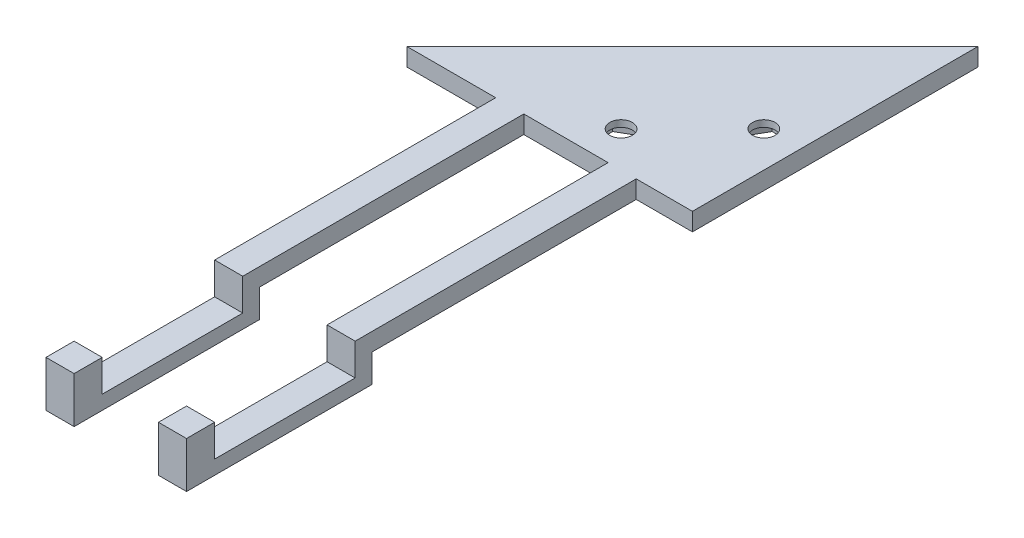
SolidWorks part; units mm, degrees
ref_plane "Front" through (0, 0, 0) normal (0, 0, 1) x (1, 0, 0)
ref_plane "Top" through (0, 0, 0) normal (0, 1, 0) x (1, 0, 0)
ref_plane "Right" through (0, 0, 0) normal (1, 0, 0) x (0, 0, -1)
sketch "Sketch1" plane through (0, 0, 0) normal (0, 1, 0) x (1, 0, 0)
  line L0 (0, 0) -> (50.8, 0)
  line L1 (-55, 0) -> (55, 0) construction
  line L2 (50.8, 0) -> (0, 50.8)
  line L3 (0, -55) -> (0, 55) construction
  line L4 (0, 50.8) -> (0, 0)
  dimension "D1" = 50.8
  dimension "D2" = 50.8
extrude "Boss-Extrude1" add sketch "Sketch1" along normal blind 3.175 contours L2 L4 L0
sketch "Sketch2" plane through (0, 3.175, 0) normal (0, 1, 0) x (1, 0, 0)
  line L0 (0, -55) -> (0, 55) construction
  line L1 (-55, 0) -> (55, 0) construction
  line L2 (0, 0) -> (25.4, 25.4) construction
  line L3 (50.8, 0) -> (0, 50.8) construction
  circle A0 centre (19.05, 6.35) radius 2
  circle A1 centre (6.35, 19.05) radius 2
  dimension "D1" = 4
  dimension "D3" = 6.35
  dimension "D2" = 19.05
extrude "Cut-Extrude1" cut sketch "Sketch2" against normal through all contours A0 | A1
sketch "Sketch3" plane through (0, 3.175, 0) normal (0, 1, 0) x (1, 0, 0)
  line L0 (0, 0) -> (25.4, 25.4) construction
  line L1 (8.3707, 15.55) -> (10.3914, 19.05)
  line L2 (10.3914, 19.05) -> (8.3707, 22.55)
  line L3 (0, 0) -> (50.8, 0)
  line L4 (50.8, 0) -> (0, 50.8)
  line L5 (0, 50.8) -> (0, 0)
  line L6 (0, 0) -> (50.8, 0)
  line L7 (50.8, 0) -> (0, 50.8)
  line L8 (0, 50.8) -> (0, 0)
  line L9 (8.3707, 22.55) -> (4.3293, 22.55)
  line L10 (4.3293, 22.55) -> (2.3086, 19.05)
  line L11 (2.3086, 19.05) -> (4.3293, 15.55)
  line L12 (4.3293, 15.55) -> (8.3707, 15.55)
  line L13 (22.55, 4.3293) -> (19.05, 2.3086)
  line L14 (19.05, 2.3086) -> (15.55, 4.3293)
  line L15 (15.55, 4.3293) -> (15.55, 8.3707)
  line L16 (15.55, 8.3707) -> (19.05, 10.3914)
  line L17 (19.05, 10.3914) -> (22.55, 8.3707)
  line L18 (22.55, 8.3707) -> (22.55, 4.3293)
  circle A0 centre (6.35, 19.05) radius 2 construction
  circle A1 centre (6.35, 19.05) radius 2
  circle A2 centre (19.05, 6.35) radius 2 construction
  circle A3 centre (19.05, 6.35) radius 2
  circle A4 centre (6.35, 19.05) radius 3.5 construction
  dimension "D2" = 7
  dimension "D1" = 0
extrude "Cut-Extrude2" cut sketch "Sketch3" along normal blind 2 from surface contours L2 L9 L10 L11 L12 L1 | L17 L18 L13 L14 L15 L16 starting at face at (6.35, 0, -21.05)
sketch "Sketch5" plane through (0, 0, 0) normal (1, 0, 0) x (0, 0, -1)
  line L0 (0, 3.1213) -> (0, -3.1213) construction
  line L1 (0, 3.175) -> (-50, 3.175)
  line L2 (0, 3.175) -> (0, 0)
  line L3 (0, 0) -> (-50, 0)
  line L4 (-50, 3.175) -> (-50, 0)
  line L5 (0, 3.175) -> (50.8, 3.175) construction
  line L6 (27.94, 0) -> (-27.94, 0) construction
  line L11 (-75, 0) -> (-80, 0)
  line L12 (-75, 0) -> (-75, 3.175)
  line L13 (-75, 3.175) -> (-80, 3.175)
  line L14 (-80, 0) -> (-80, 3.175)
  line L15 (-80, 0) -> (-47, 0)
  line L16 (-80, 0) -> (-80, -5)
  line L17 (-80, -5) -> (-47, -5)
  line L18 (-47, 0) -> (-47, -5)
  line L20 (-75, 0) -> (-50, 0)
  line L21 (-75, 0) -> (-75, -2.5)
  line L22 (-75, -2.5) -> (-50, -2.5)
  line L23 (-50, 0) -> (-50, -2.5)
  dimension "D1" = 3.175
  dimension "D2" = 30
  dimension "D3" = 5
  dimension "D4" = 50
  dimension "D5" = 3
  dimension "D6" = 5
  dimension "D7" = 2.5
extrude "Boss-Extrude2" add sketch "Sketch5" along normal blind 5 from offset 10 contours L14 L11 L12 L13 | L18 L3 L15 L11 L16 L17 | L1 L4 L3 L2 region at (0, 1.5875, 25) region at (0, -3.2622, 64.1098) region at (0, 1.5875, 77.5)
extrude "Boss-Extrude3" add sketch "Sketch5<3>" along normal blind 5 from offset 30 contours L18 L3 L15 L11 L16 L17 | L1 L4 L3 L2 | L13 L14 L11 L12 region at (0, 1.5875, 25) region at (0, -3.2622, 64.1098)
sketch "Sketch5<3>" plane through (0, 0, 0) normal (1, 0, 0) x (0, 0, -1) same geometry as "Sketch5"
mirror "Mirror1" about plane through (0, 0, 0) normal (1, 0, 0) of bodies 105
sketch "Sketch6" plane through (0, 0, 0) normal (0, 1, 0) x (1, 0, 0)
  line L0 (0, -4.4963) -> (0, 4.4963) construction
  line L1 (0, 52.4046) -> (69.501, 52.4046)
  line L2 (0, 52.4046) -> (0, -84.2009)
  line L3 (0, -84.2009) -> (69.501, -84.2009)
  line L4 (69.501, 52.4046) -> (69.501, -84.2009)
extrude "Cut-Extrude3" cut sketch "Sketch6" against normal through all both and the other way through all
